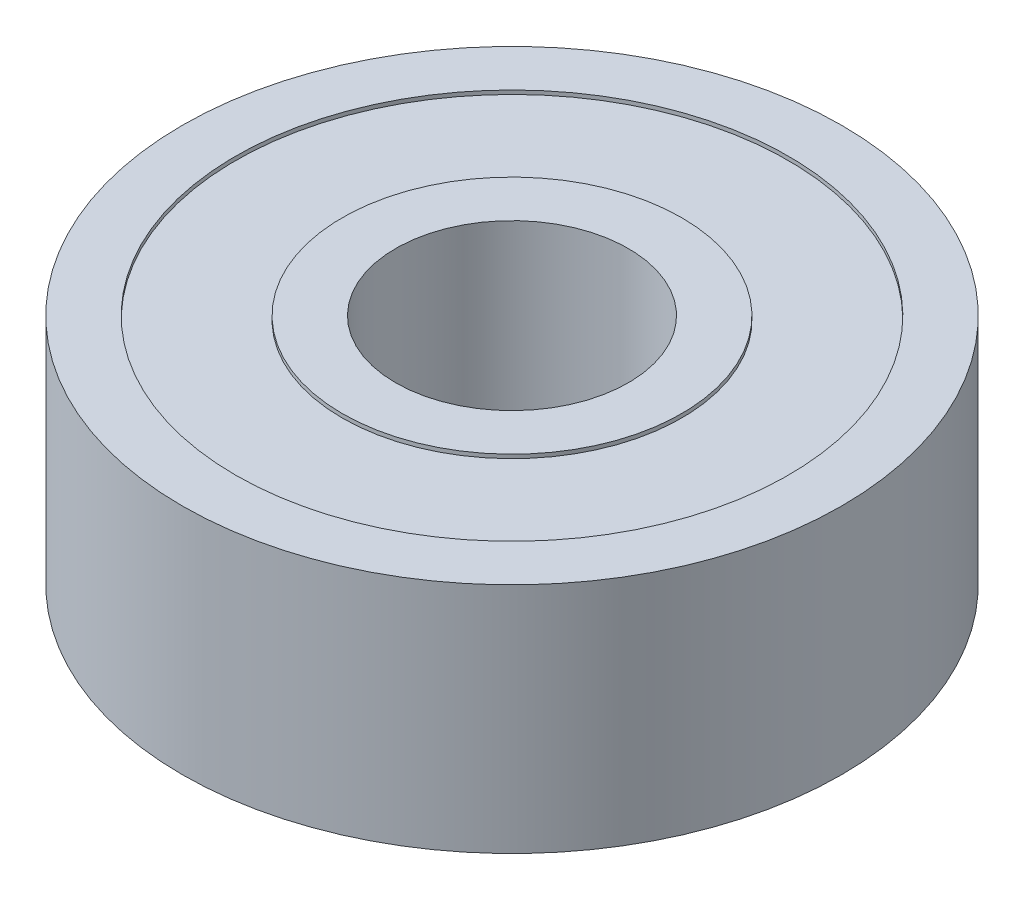
SolidWorks part; units mm, degrees
ref_plane "Front plane" through (0, 0, 0) normal (0, 0, 1) x (1, 0, 0)
ref_plane "Top plane" through (0, 0, 0) normal (0, 1, 0) x (1, 0, 0)
ref_plane "Right plane" through (0, 0, 0) normal (1, 0, 0) x (0, 0, -1)
ref_axis "Axis X" through (0, 0, 0) along (1, 0, 0)
ref_axis "Axis Y" through (0, 0, 0) along (0, 1, 0)
ref_axis "Axis Z" through (0, 0, 0) along (0, 0, 1)
sketch "Sketch1" plane through (0, 0, 0) normal (0, 1, 0) x (1, 0, 0)
  circle A0 centre (0, 0) radius 8.5
  circle A1 centre (0, 0) radius 3
  dimension "D1" = 17
  dimension "D2" = 6
extrude "Extrude1" add sketch "Sketch1" along normal blind 6
sketch "Sketch2" plane through (0, 6, 0) normal (0, 1, 0) x (1, 0, 0)
  circle A2 centre (0, 0) radius 7.125
  circle A3 centre (0, 0) radius 7.125
  circle A5 centre (0, 0) radius 4.375
  circle A6 centre (0, 0) radius 4.375
  dimension "D1" = 1.375
  dimension "D2" = 1.375
extrude "Extrude2" cut sketch "Sketch2" against normal blind 0.1
sketch "Sketch3" plane through (0, 0, 0) normal (0, -1, 0) x (1, 0, 0)
  circle A2 centre (0, 0) radius 7.125
  circle A3 centre (0, 0) radius 7.125
  circle A5 centre (0, 0) radius 4.375
  circle A6 centre (0, 0) radius 4.375
  dimension "D1" = 1.375
  dimension "D2" = 1.375
extrude "Extrude3" cut sketch "Sketch3" against normal blind 0.1
equation "\"motor_D\"= 30'Motor diameter"
equation "\"motor_H\"= 13'Motor heigh"
equation "\"motor_d1\"= 25.4558'Seating diameter of screws on the fixed part of the motor"
equation "\"motor_s1\"= 2'Screws diameter on the fixed part of motor"
equation "\"motor_a2\"= 10'Seating parameter in rectangle of screws on the moving part of the motor"
equation "\"motor_s2\"= 2'Screws diameter on the moving part of motor"
equation "\"motor_Dc\"= 5'Central hole diameter of motor"
equation "\"bearing_d1\"= 6'Bearing inner diameter"
equation "\"bearing_d2\"= 17'Bearing external diameter"
equation "\"bearing h\"= 6'Bearing heigh"
equation "\"pin_d\"= 2'Pin diameter"
equation "\"pin_h\"= 12'Pin heigh"
equation "\"magnet_d1\"= 5'Magnet inner diameter"
equation "\"magnet_d2\"= 9.5'Magnet external diameter"
equation "\"magnet_h\"= 3'Magnet heigh"
equation "\"motor_b2\"= 22'Seating parameter in rectangle of screws on the moving part of the motor"
equation "\"motor_d2\"= 0'Seating diameter of screws on the moving part of the motor (if this parameter is not determine, write 0)"
equation "\"motor_cmd\"= 12'Central magnet mount diameter"
equation "\"motor_cmh\"= 1.4'Central magnet mount heigh (if not write 0)"
equation "\"motor_whR\"= 10'Distance from center of motor to wires"
equation "\"D1@Sketch1\"=\"bearing_d2\""
equation "\"D2@Sketch1\"=\"bearing_d1\""
equation "\"D1@Extrude1\"=\"bearing h\""
equation "\"D1@Sketch2\"=(\"bearing_d2\"-\"bearing_d1\")/2/4"
equation "\"D2@Sketch2\"=\"D1@Sketch2\""
equation "\"D1@Extrude2\"=0.1"
equation "\"D2@Sketch3\"=(\"bearing_d2\"-\"bearing_d1\")/2/4"
equation "\"D1@Sketch3\"=\"D2@Sketch3\""
equation "\"print_offset\"= 0.2'Offset for printing holes"
equation "\"ft_sensor_d1\"= 9.8"
equation "\"ft_sensor_d2\"= 24.9"
equation "\"ft_sensor_d3\"= 22.6'Inner diameter of "
equation "\"ft_sensor_h\"= 7.1"
equation "\"ft_sensor_whD\" = 5"
